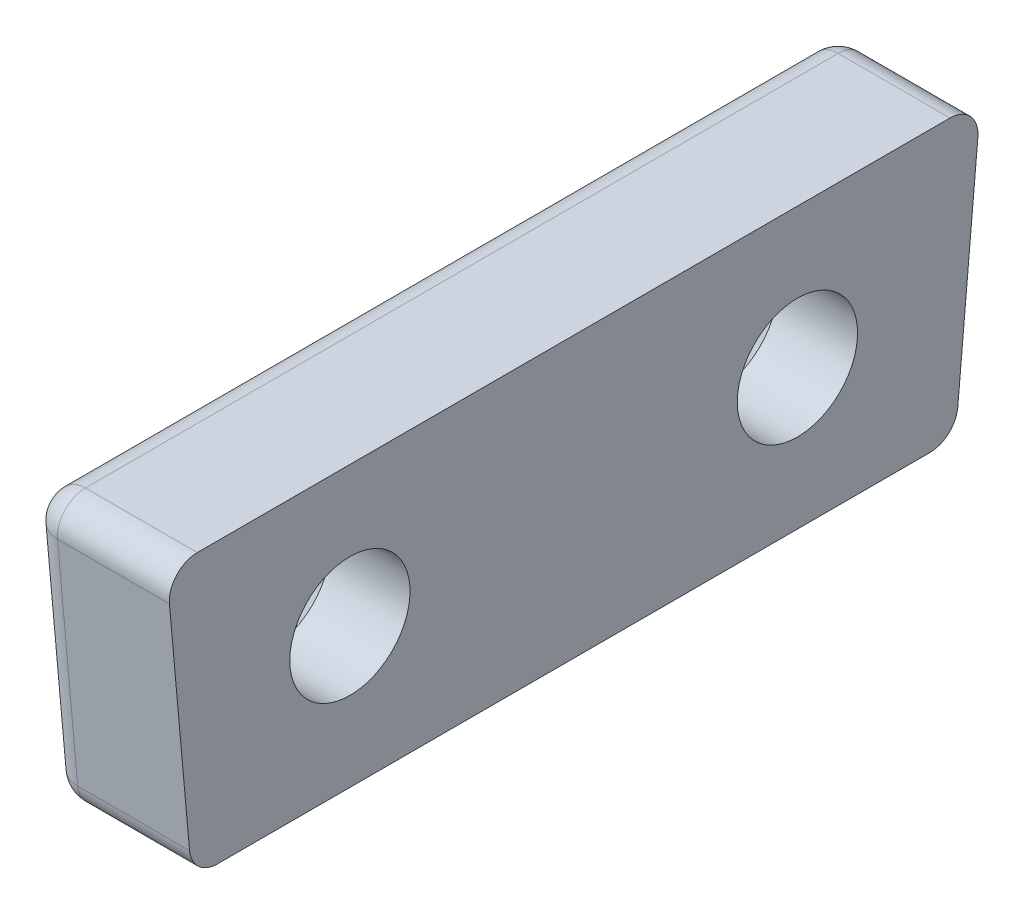
SolidWorks part; units mm, degrees
ref_plane "前视基准面" through (0, 0, 0) normal (0, 0, 1) x (1, 0, 0)
ref_plane "上视基准面" through (0, 0, 0) normal (0, 1, 0) x (1, 0, 0)
ref_plane "右视基准面" through (0, 0, 0) normal (1, 0, 0) x (0, 0, -1)
other "Configuration Table"
sketch "草图1" plane through (0, 0, 0) normal (1, 0, 0) x (0, 0, -1)
  line L0 (-15, 23) -> (15, 23)
  line L1 (-15, 23) -> (-16.9317, 1.5228)
  line L2 (15.4497, 18) -> (16.3491, 8)
  line L3 (22, 13) -> (22, 18) construction
  line L4 (22, 18) -> (15.4497, 18)
  line L5 (16.3491, 8) -> (43.6509, 8)
  line L6 (30, 8) -> (30, 18) construction
  line L7 (44.5503, 18) -> (15.4497, 18)
  line L8 (44.5503, 18) -> (43.6509, 8)
  line L9 (38, 18) -> (44.5503, 18)
  circle A0 centre (0, 0) radius 17
  point P6 (0, 23)
  point P10 (38, 13)
  dimension "D1" = 34
  dimension "D2" = 30
  dimension "D3" = 23
  dimension "D4" = 22
  dimension "D5" = 13
  dimension "D6" = 5
  dimension "D7" = 16
  dimension "D8" = 5
extrude "凸台-拉伸1" add sketch "草图1" along normal blind 5 contours L8 L7 L4 L2 L5 region at (0, 13.0532, -30)
hole_wizard "M4 十字槽沉头木螺钉的锥形沉头孔1" positions "草图3" profile "草图4" countersink size "M4" standard "GB" end condition through all
sketch "草图3" plane through (0, 0, 0) normal (-1, 0, 0) x (0, 0, 1)
  point P3 (-38, 13)
  point P6 (-22, 13)
sketch "草图4" plane through (0, 13, -38) normal (0, 1, 0) x (0, 0, 1)
  line L0 (0, 0) -> (0, 5)
  line L1 (0, 5) -> (2.15, 5)
  line L2 (2.15, 5) -> (2.15, 2.15)
  line L3 (2.15, 2.15) -> (4.3, 0)
  line L5 (4.3, 0) -> (0, 0)
  line L6 (-2.15, 2.15) -> (-4.3, 0) construction
  line L11 (0, -6.35) -> (0, 107.95) construction
  dimension "通孔孔直径" = 4.3
  dimension "通孔孔深度" = 5
  dimension "近端锥形沉头孔直径" = 8.6
  dimension "近端锥形沉头孔角度" = 90
fillet "圆角1" radius 1 8 edges at (0, 8, -30) (0, 18, -30) (0, 13, -44.1006) (0, 13, -15.8994) (2.5, 18, -15.4497) (2.5, 8, -16.3491) (2.5, 8, -43.6509) (2.5, 18, -44.5503)
